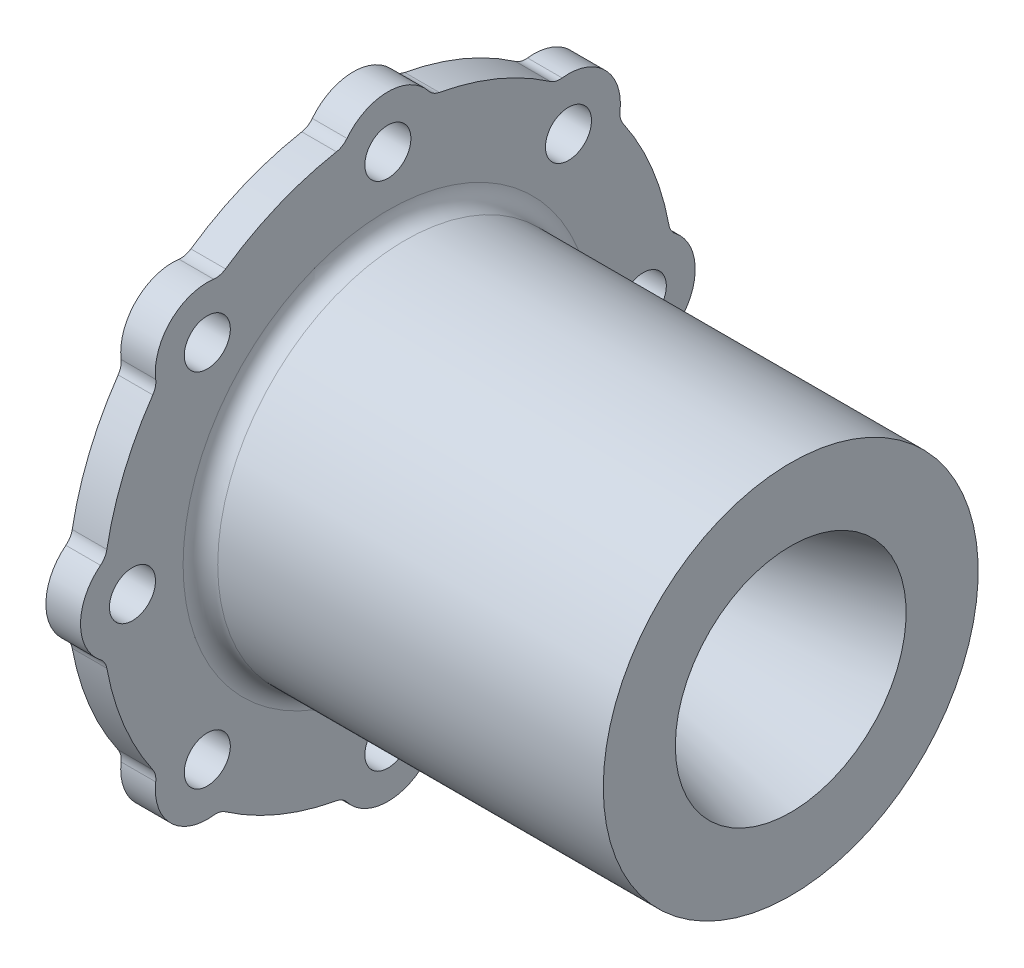
SolidWorks part; units mm, degrees
ref_plane "Front Plane" through (0, 0, 0) normal (0, 0, 1) x (1, 0, 0)
ref_plane "Top Plane" through (0, 0, 0) normal (0, 1, 0) x (1, 0, 0)
ref_plane "Right Plane" through (0, 0, 0) normal (1, 0, 0) x (0, 0, -1)
sketch "Sketch1" plane through (0, 0, 0) normal (0, 0, 1) x (1, 0, 0)
  line L20 (0, 0) -> (32.997, 0) construction
  line L33 (15.4847, 6.946) -> (26.9147, 6.946)
  line L34 (15.4847, 6.946) -> (0, 25.4)
  line L37 (0, 25.4) -> (0, 66.87)
  line L38 (0, 66.87) -> (5.08, 66.87)
  line L39 (5.08, 66.87) -> (5.08, 27.5)
  line L43 (64.1755, 27.5) -> (64.1755, 16.93)
  line L52 (64.1755, 16.93) -> (26.9147, 6.946)
  line L53 (64.1755, 27.5) -> (5.08, 27.5)
  point P1 (2.54, 66.87)
  point P12 (15.4847, 6.946)
  point P24 (26.9147, 6.946)
  dimension "D1" = 6.946
  dimension "D2" = 25.4
  dimension "D5" = 5.08
  dimension "D10" = 15
  dimension "D8" = 16.93
  dimension "D3" = 27.5
  dimension "D4" = 66.87
  dimension "D6" = 11.43
  dimension "D7" = 50
revolve "Nozzle" add sketch "Sketch1" angle 360 about L20
fillet "Rao outlet radius" radius 5.3067 1 edges at (26.9147, 0, 6.946)
sketch "Sketch2" plane through (0, 0, 0) normal (-1, 0, 0) x (0, 0, 1)
  point P0 (37.465, 0)
  point P1 (26.4918, -26.4918)
  point P5 (0, -37.465)
  point P6 (-26.4918, -26.4918)
  point P7 (-37.465, 0)
  point P8 (-26.4918, 26.4918)
  point P9 (0, 37.465)
  point P10 (26.4918, 26.4918)
  point P11 (0, 0)
  dimension "D1" = 37.465
hole_wizard "1/4 Clearance Hole1" positions "Sketch2" profile "Sketch3" hole size "1/4" standard "ANSI Inch" end condition through all
sketch "Sketch3" plane through (0, 0, 37.465) normal (0, 1, 0) x (0, 0, 1)
  line L0 (0, 0) -> (0, 64.1755)
  line L1 (0, 64.1755) -> (3.3782, 64.1755)
  line L2 (3.3782, 64.1755) -> (3.3782, 0)
  line L5 (3.3782, 0) -> (0, 0)
  line L11 (0, -6.35) -> (0, 107.95) construction
  dimension "Thru Hole Dia." = 6.7564
  dimension "Thru Hole Depth" = 64.1755
sketch "Sketch5" plane through (0, 0, 0) normal (1, 0, 0) x (0, 0, -1)
  line L0 (0, 0) -> (0, 85.5504) construction
  arc A32 (6.0027, 42.1589) -> (-6.0027, 42.1589) centre (0, 37.465) ccw
  arc A33 (17.8531, 37.9172) -> (7.5462, 41.225) centre (0, 0) ccw
  arc A51 (-7.5462, 41.225) -> (-14.1874, 39.4356) centre (0, 0) ccw
  arc A69 (6.0027, 42.1589) -> (7.5462, 41.225) centre (8.0035, 43.7235) ccw
  arc A70 (-6.0027, 42.1589) -> (-7.5462, 41.225) centre (-8.0035, 43.7235) cw
  arc A72 (34.0554, 25.5663) -> (25.5663, 34.0554) centre (26.4918, 26.4918) ccw
  arc A73 (39.4356, 14.1874) -> (34.4865, 23.8145) centre (0, 0) ccw
  arc A74 (23.8145, 34.4865) -> (17.8531, 37.9172) centre (0, 0) ccw
  arc A75 (34.0554, 25.5663) -> (34.4865, 23.8145) centre (36.5765, 25.2578) ccw
  arc A76 (25.5663, 34.0554) -> (23.8145, 34.4865) centre (25.2578, 36.5765) cw
  arc A77 (42.1589, -6.0027) -> (42.1589, 6.0027) centre (37.465, 0) ccw
  arc A78 (37.9172, -17.8531) -> (41.225, -7.5462) centre (0, 0) ccw
  arc A79 (41.225, 7.5462) -> (39.4356, 14.1874) centre (0, 0) ccw
  arc A80 (42.1589, -6.0027) -> (41.225, -7.5462) centre (43.7235, -8.0035) ccw
  arc A81 (42.1589, 6.0027) -> (41.225, 7.5462) centre (43.7235, 8.0035) cw
  arc A82 (25.5663, -34.0554) -> (34.0554, -25.5663) centre (26.4918, -26.4918) ccw
  arc A83 (14.1874, -39.4356) -> (23.8145, -34.4865) centre (0, 0) ccw
  arc A84 (34.4865, -23.8145) -> (37.9172, -17.8531) centre (0, 0) ccw
  arc A85 (25.5663, -34.0554) -> (23.8145, -34.4865) centre (25.2578, -36.5765) ccw
  arc A86 (34.0554, -25.5663) -> (34.4865, -23.8145) centre (36.5765, -25.2578) cw
  arc A87 (-6.0027, -42.1589) -> (6.0027, -42.1589) centre (0, -37.465) ccw
  arc A88 (-14.2148, -39.4257) -> (-7.5462, -41.225) centre (0, 0) ccw
  arc A89 (7.5462, -41.225) -> (14.1874, -39.4356) centre (0, 0) ccw
  arc A90 (-6.0027, -42.1589) -> (-7.5462, -41.225) centre (-8.0035, -43.7235) ccw
  arc A91 (6.0027, -42.1589) -> (7.5462, -41.225) centre (8.0035, -43.7235) cw
  arc A92 (-34.0554, -25.5663) -> (-25.5663, -34.0554) centre (-26.4918, -26.4918) ccw
  arc A93 (-37.9194, -17.8486) -> (-34.4865, -23.8145) centre (0, 0) ccw
  arc A94 (-23.8145, -34.4865) -> (-14.2148, -39.4257) centre (0, 0) ccw
  arc A95 (-34.0554, -25.5663) -> (-34.4865, -23.8145) centre (-36.5765, -25.2578) ccw
  arc A96 (-25.5663, -34.0554) -> (-23.8145, -34.4865) centre (-25.2578, -36.5765) cw
  arc A97 (-42.1589, 6.0027) -> (-42.1589, -6.0027) centre (-37.465, 0) ccw
  arc A98 (-39.4483, 14.1519) -> (-41.225, 7.5462) centre (0, 0) ccw
  arc A99 (-41.225, -7.5462) -> (-37.9194, -17.8486) centre (0, 0) ccw
  arc A100 (-42.1589, 6.0027) -> (-41.225, 7.5462) centre (-43.7235, 8.0035) ccw
  arc A101 (-42.1589, -6.0027) -> (-41.225, -7.5462) centre (-43.7235, -8.0035) cw
  arc A102 (-25.5663, 34.0554) -> (-34.0554, 25.5663) centre (-26.4918, 26.4918) ccw
  arc A103 (-14.1874, 39.4356) -> (-23.8145, 34.4865) centre (0, 0) ccw
  arc A104 (-34.4865, 23.8145) -> (-39.4483, 14.1519) centre (0, 0) ccw
  arc A105 (-25.5663, 34.0554) -> (-23.8145, 34.4865) centre (-25.2578, 36.5765) ccw
  arc A106 (-34.0554, 25.5663) -> (-34.4865, 23.8145) centre (-36.5765, 25.2578) cw
  point P69 (0, 0)
  point P78 (-6.5261, 41.3988)
  dimension "D3" = 41.91
  dimension "D4" = 2.54
  dimension "D5" = 37.465
  dimension "D6" = 37.465
  dimension "D1" = 8
extrude "Cut-Extrude1" cut sketch "Sketch5" along normal up to surface (5.08 mm away) flip side to cut up to face at (5.08, 0, 40.8432)
fillet "Fillet1" radius 2.54 1 edges at (5.08, 0, 27.5)
fillet "Rao Inlet radius" radius 20.838 1 edges at (15.4847, 0, 6.946)
equation "\"radius\"= 1in"
equation "\"Flange\"= 0.55in"
equation "\"Length\"= 2cm"
equation "\"Flange_Thickness\"= 0.2in"
equation "\"offset\"= 0.625cm"
equation "\"D2@Sketch1\"=\"radius\""
equation "\"throat\"= 0.6946cm"
equation "\"hole_dia\"= 0.66cm"
equation "\"D1@Sketch1\"=\"throat\""
equation "\"D5@Sketch1\"=\"Flange_Thickness\""
equation "\"Seal_dia\"= 2.5cm"
equation "\"Seal_depth\"= 0.1cm"
equation "\"Seal_width\"= 0.15cm"
equation "\"Nozzle_angle\"= 15"
equation "\"D10@Sketch1\"=\"Nozzle_angle\""
equation "\"nozzle_length\"= 6.34"
equation "\"bolt_head_dia\"=2.3795"
equation "\"bolt_rad\"= \"radius\" + 0.5 * \"Flange\" + 0.2in"
equation "\"scallop_inner_dia\"= 3.3in"
equation "\"exit_rad\"= 1.693cm"
equation "\"D8@Sketch1\"=\"exit_rad\""
equation "\"outside_dia\"= 2.75cm"
equation "\"D3@Sketch1\"=\"outside_dia\""
equation "\"D4@Sketch1\"=\"outside_dia\"+\"Flange\"+\"Buffer\""
equation "\"Scallop_OD\"= 0.6in"
equation "\"D3\"= \"Scallop_OD\" / 2"
equation "\"D4\"= \"scallop_inner_dia\" / 2"
equation "\"D2@Sketch5\"=\"Scallop_OD\"/2"
equation "\"D3@Sketch5\"=\"scallop_inner_dia\"/2"
equation "\"D6@Sketch5\"=\"bolt_rad\""
equation "\"D1@Sketch2\"=\"bolt_rad\""
equation "\"Buffer\"= 1in"
equation "\"D1@Rao Inlet radius\"=3*\"throat\""
equation "\"D1@Rao outlet radius\"=2 * 0.382 * \"throat\""
